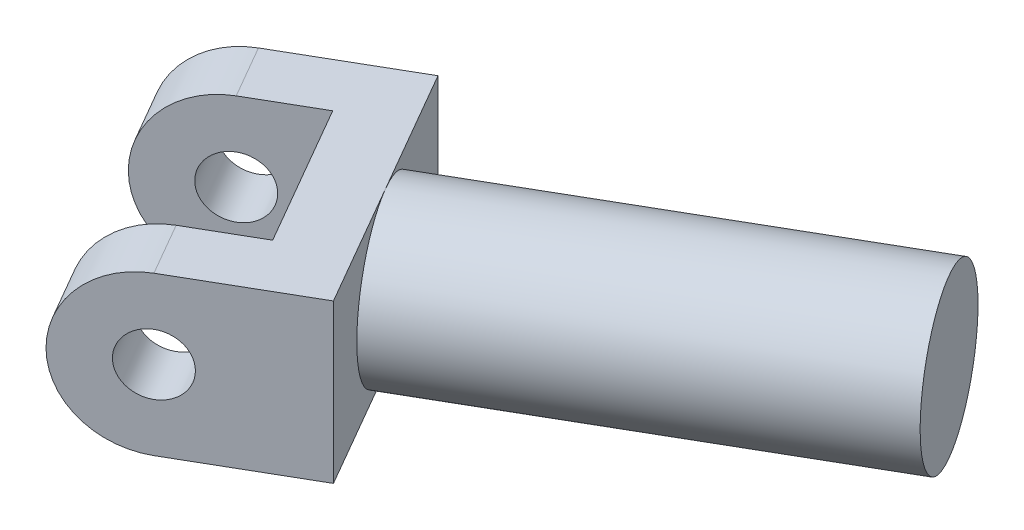
SolidWorks part; units mm, degrees
material "Chrome Stainless Steel"
ref_plane "Front Plane" through (0, 0, 0) normal (0, 0, 1) x (1, 0, 0)
ref_plane "Top Plane" through (0, 0, 0) normal (0, 1, 0) x (1, 0, 0)
ref_plane "Right Plane" through (0, 0, 0) normal (1, 0, 0) x (0, 0, -1)
sketch "Sketch1" plane through (0, 0, 0) normal (0, 1, 0) x (1, 0, 0)
  line L0 (86.6025, 150) -> (0, 0) construction
  line L1 (173.2051, 0) -> (0, 0) construction
  line L2 (86.6025, 150) -> (103.923, 160)
  line L3 (158.0737, 16.2083) -> (93.0737, 128.7917)
  line L4 (181.5544, 35.5385) -> (194.8557, 12.5) construction
  line L5 (173.2051, 0) -> (194.8557, 12.5) construction
  line L6 (86.6025, -150) -> (173.2051, 0) construction
  line L7 (173.2051, 0) -> (159.9038, 23.0385) construction
  line L8 (159.9038, 23.0385) -> (181.5544, 35.5385) construction
  line L9 (181.5544, 35.5385) -> (121.5544, 139.4615) construction
  line L10 (121.5544, 139.4615) -> (99.9038, 126.9615) construction
  line L12 (86.6025, 150) -> (-86.6025, 150) construction
  line L13 (-86.6025, 150) -> (-99.9038, 126.9615) construction
  line L14 (-99.9038, 126.9615) -> (-121.5544, 139.4615) construction
  line L15 (-121.5544, 139.4615) -> (-181.5544, 35.5385) construction
  line L16 (-181.5544, 35.5385) -> (-159.9038, 23.0385) construction
  line L17 (-159.9038, 23.0385) -> (-173.2051, 0) construction
  line L18 (-173.2051, 0) -> (-86.6025, -150) construction
  line L19 (-86.6025, -150) -> (-60, -150) construction
  line L20 (-60, -150) -> (-60, -175) construction
  line L21 (-60, -175) -> (60, -175) construction
  line L22 (60, -175) -> (60, -150) construction
  line L23 (60, -150) -> (86.6025, -150) construction
  line L24 (22.799, 39.489) -> (45.598, 0)
  line L25 (22.799, 39.489) -> (86.6025, 150)
  line L26 (151.5544, 87.5) -> (34.1985, 19.7445) construction
  line L27 (114.7243, 141.2917) -> (103.923, 160)
  line L28 (114.7243, 141.2917) -> (93.0737, 128.7917)
  line L29 (45.598, 0) -> (173.2051, 0)
  line L30 (173.2051, 0) -> (190.5256, 10)
  line L31 (179.7243, 28.7083) -> (190.5256, 10)
  line L32 (179.7243, 28.7083) -> (158.0737, 16.2083)
  line L33 (0, 0) -> (131.7313, -228.1653) construction
  line L34 (140.7291, 81.25) -> (272.4604, -146.9153) construction
  point P4 (101.6025, 168.75)
  point P22 (88.923, 130.7115)
  point P26 (75.6218, 153.75)
  point P34 (125.5737, 72.5)
  dimension "D1" = 162.5
extrude "Boss-Extrude1" add sketch "Sketch1" along normal mid plane 50
ref_plane "Plane1" through (140.7291, 0, -81.25) normal (0.5, 0, 0.866) x (0.866, 0, -0.5)
sketch "Sketch2" plane through (140.7291, 0, -81.25) normal (0.5, 0, 0.866) x (0.866, 0, -0.5)
  line L0 (0, 0) -> (0, -100.0987) construction
  line L1 (12.5, 0) -> (-12.5, 0) construction
  circle A0 centre (0, 0) radius 8
extrude "Cut-Extrude1" cut sketch "Sketch2" against normal mid plane 220
sketch "Sketch3" plane through (140.7291, 0, -81.25) normal (0.5, 0, 0.866) x (0.866, 0, -0.5)
  line L0 (0, 18) -> (-12.5, 18)
  line L1 (-12.5, 25) -> (-12.5, -25) construction
  line L2 (0, -18) -> (-12.5, -18)
  line L3 (-12.5, 18) -> (-12.5, 31.3122)
  line L4 (-12.5, 31.3122) -> (23.9059, 31.3122)
  line L5 (23.9059, 31.3122) -> (23.9059, -29.5052)
  line L6 (-12.5, -29.5052) -> (23.9059, -29.5052)
  line L7 (-12.5, -18) -> (-12.5, -29.5052)
  arc A0 (0, -18) -> (0, 18) centre (0, 0) ccw
extrude "Cut-Extrude2" cut sketch "Sketch3" against normal mid plane 300
ref_plane "Plane2" through (173.2291, 0, -24.9583) normal (0.5, 0, 0.866) x (0.866, 0, -0.5)
sketch "Sketch4" plane through (173.2291, 0, -24.9583) normal (0.5, 0, 0.866) x (0.866, 0, -0.5)
  line L2 (7.5, 16.3631) -> (7.5, 2.7839)
  line L3 (7.5, -2.7839) -> (7.5, -16.3631)
  line L7 (-12.5, 18) -> (0, 18)
  line L8 (-12.5, 31.3122) -> (-12.5, 18)
  line L9 (23.9059, 31.3122) -> (-12.5, 31.3122)
  line L10 (23.9059, -29.5052) -> (23.9059, 31.3122)
  line L11 (-12.5, -29.5052) -> (23.9059, -29.5052)
  line L12 (-12.5, -18) -> (-12.5, -29.5052)
  line L13 (0, -18) -> (-12.5, -18)
  arc A0 (7.5, -2.7839) -> (7.5, 2.7839) centre (0, 0) ccw
  arc A1 (0, -18) -> (0, 18) centre (0, 0) ccw
  arc A2 (7.5, -16.3631) -> (7.5, 16.3631) centre (0, 0) ccw
  dimension "D1" = 0
extrude "Boss-Extrude2" add sketch "Sketch4" along normal blind 21.6025
mirror "Mirror2" about plane through (140.7291, 0, -81.25) normal (0.5, 0, 0.866) of "Boss-Extrude2"
sketch "Sketch5" plane through (34.1985, 0, -19.7445) normal (-0.866, 0, 0.5) x (0.5, 0, 0.866)
  circle A0 centre (0, 0) radius 13
extrude "Cut-Extrude3" cut sketch "Sketch5" against normal blind 50
sketch "Sketch6" plane through (77.4998, 0, -44.7445) normal (-0.866, 0, 0.5) x (0.5, 0, 0.866)
  circle A1 centre (0, 0) radius 13
  circle A2 centre (0, 0) radius 13
  dimension "D1" = 0
extrude "Boss-Extrude3" add sketch "Sketch6" along normal blind 100 separate body
sketch "Sketch7" plane through (140.7291, 0, -81.25) normal (0.5, 0, 0.866) x (0.866, 0, -0.5)
  circle A0 centre (-162.5, 0) radius 5
extrude "Cut-Extrude4" cut sketch "Sketch7" against normal mid plane 100
sketch "Sketch8" plane through (140.7291, 0, -81.25) normal (0.5, 0, 0.866) x (0.866, 0, -0.5)
  circle A0 centre (-162.5, 0) radius 13
  circle A1 centre (-162.5, 0) radius 5
extrude "Boss-Extrude4" add sketch "Sketch8" along normal mid plane 26
sketch "Sketch9" plane through (140.7291, 0, -81.25) normal (0.5, 0, 0.866) x (0.866, 0, -0.5)
  line L0 (-162.5, 18.8341) -> (-162.5, 13)
  line L1 (-162.5, -13) -> (-162.5, -19.8118)
  arc A0 (-162.5, 13) -> (-162.5, -13) centre (-162.5, 0) ccw
  arc A1 (-162.5, 18.8341) -> (-162.5, -18.8341) centre (-162.5, 0) ccw
extrude "Cut-Extrude5" cut sketch "Sketch9" against normal mid plane 56 contours L0 A1 L1 A0 region at (-0.3647, 15.917, 0.2106)
delete or keep bodies "Body-Delete/Keep 1" type delete bodies bodies 106
ref_plane "Plane3" through (0, 0, 0) normal (0.5, 0, 0.866) x (0.866, 0, -0.5)
ref_axis "Axis1" through (-8.6651, 0, -15.0083) along (0.5, 0, 0.866)
ref_axis "Axis2" through (24.2499, 0, -14.0007) along (0.866, 0, -0.5)
ref_plane "Plane4" through (6.75, 0, 11.6913) normal (0.5, 0, 0.866) x (0.866, 0, -0.5)
sketch "Sketch10" plane through (6.75, 0, 11.6913) normal (0.5, 0, 0.866) x (0.866, 0, -0.5)
  line L0 (0, 13) -> (21.6263, 13)
  line L1 (89.489, 13) -> (0, 13) construction
  line L2 (21.6263, 13) -> (21.6263, -13)
  line L3 (0, -13) -> (21.6263, -13)
  circle A0 centre (0, 0) radius 5 construction
  circle A1 centre (0, 0) radius 13
  arc A2 (0, 13) -> (0, -13) centre (0, 0) ccw
  circle A3 centre (0, 0) radius 5
  dimension "D1" = 0
extrude "Boss-Extrude5" add sketch "Sketch10" along normal blind 10 separate body
pattern_circular "CirPattern2" count 2 over 360 about axis through (24.2499, 0, -14.0007) along (0.866, 0, -0.5) of bodies 111
sketch "Sketch11" plane through (18.7289, 0, -10.8131) normal (0.866, 0, -0.5) x (-0.5, 0, -0.866)
  line L1 (-23.5, 13) -> (23.5, 13)
  line L2 (-23.5, 13) -> (-23.5, -13)
  line L3 (-23.5, -13) -> (23.5, -13)
  line L4 (23.5, 13) -> (23.5, -13)
extrude "Boss-Extrude6" add sketch "Sketch11" against normal blind 10 separate body
sketch "Sketch12" plane through (18.7289, 0, -10.8131) normal (0.866, 0, -0.5) x (-0.5, 0, -0.866)
  circle A0 centre (0, 0) radius 13 construction
  circle A1 centre (0, 0) radius 13
extrude "Boss-Extrude7" add sketch "Sketch12" along normal blind 67.8628 separate body
combine bodies "Combine2" operation type add bodies to combine 112 113 114 111
delete or keep bodies "Body-Delete/Keep 2" type delete bodies bodies 110
ref_plane "Plane5" through (0, 0, 0) normal (0, -1, 0) x (0.866, 0, -0.5)
